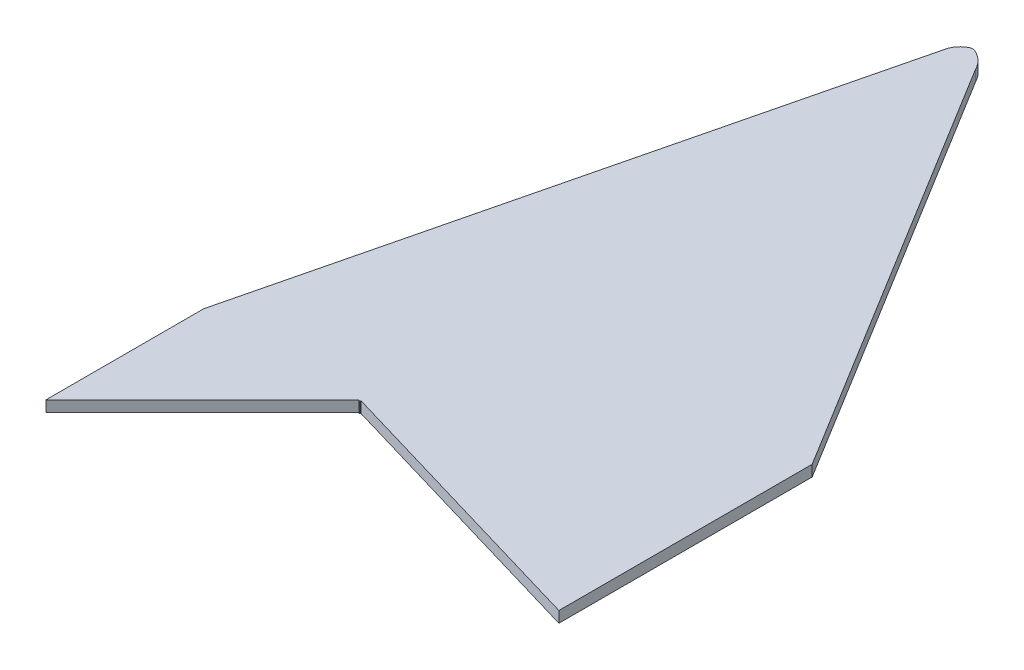
SolidWorks part; units mm, degrees
ref_plane "Front Plane" through (0, 0, 0) normal (0, 0, 1) x (1, 0, 0)
ref_plane "Top Plane" through (0, 0, 0) normal (0, 1, 0) x (1, 0, 0)
ref_plane "Right Plane" through (0, 0, 0) normal (1, 0, 0) x (0, 0, -1)
sketch "Sketch2" plane through (0, 0, 0) normal (0, 1, 0) x (1, 0, 0)
  line L0 (-2.5438, -35.2008) -> (-20.5215, -53.1817)
  line L1 (-20.5215, -53.1817) -> (-20.5215, -35.0945)
  line L2 (-20.5215, -35.0945) -> (-3.769, 33.269)
  line L3 (-2.3618, -35.2008) -> (29.835, -44.6948)
  line L4 (29.835, -44.6948) -> (29.835, -15.6302)
  line L5 (29.835, -15.6302) -> (-0.0038, 32.9283)
  arc A0 (-2.5438, -35.2008) -> (-2.3618, -35.2008) centre (-2.4528, -35.2008) ccw
  arc A1 (-3.769, 33.269) -> (-2.4789, 34.8084) centre (-1.5595, 32.7276) cw
  arc A2 (-2.4789, 34.8084) -> (-1.9529, 34.8084) centre (-2.2159, 34.2132) cw
  arc A4 (-2.5464, -35.2231) -> (-2.3644, -35.2231) centre (-2.4554, -35.1984) ccw
  arc A5 (-1.9529, 34.8084) -> (-0.0038, 32.9283) centre (-3.5428, 31.2099) cw
  point P16 (36.1455, -15.1794)
  point P17 (29.835, -15.6302)
extrude "Boss-Extrude1" add sketch "Sketch2" along normal blind 1.27 contours A5 A2 A1 L2 L1 L0 A0 A4 L3 L4 L5 region at (4.3161, 0, 13.9061)
